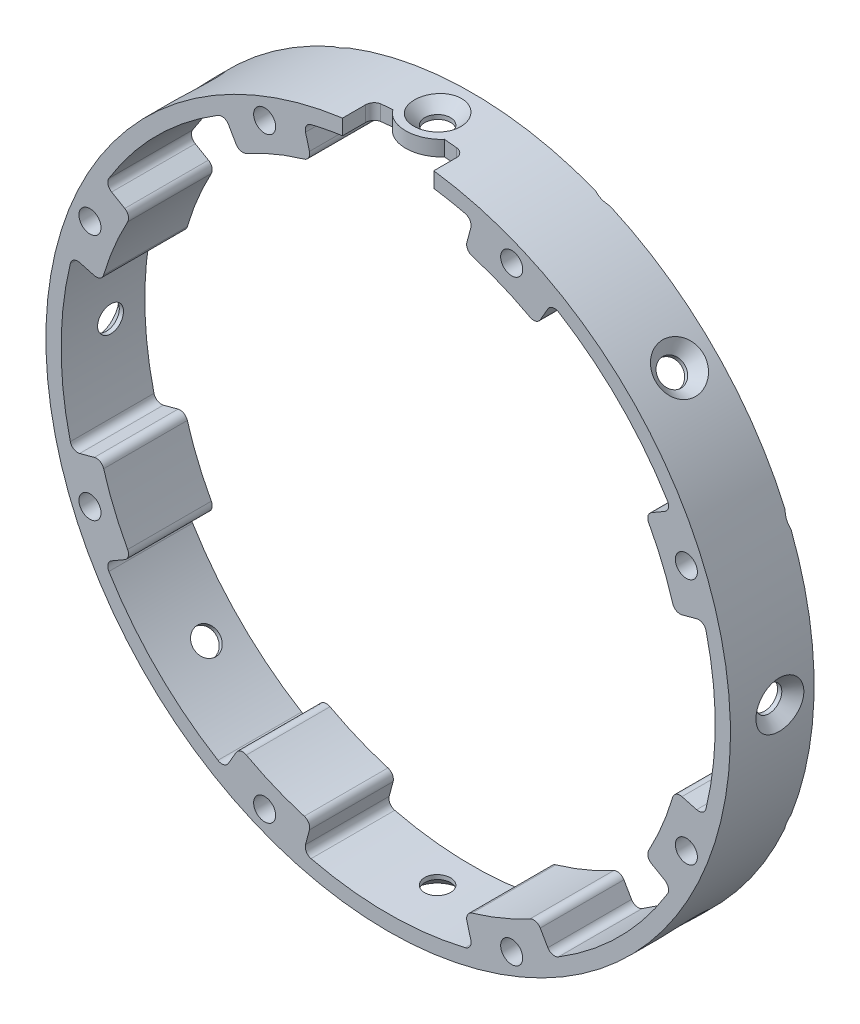
SolidWorks part; units mm, degrees
ref_plane "前视基准面" through (0, 0, 0) normal (0, 0, 1) x (1, 0, 0)
ref_plane "上视基准面" through (0, 0, 0) normal (0, 1, 0) x (1, 0, 0)
ref_plane "右视基准面" through (0, 0, 0) normal (1, 0, 0) x (0, 0, -1)
sketch "草图1" plane through (0, 0, 0) normal (0, 0, 1) x (1, 0, 0)
  line L0 (11.1292, 41.5348) -> (10.0939, 37.6711)
  line L17 (21.5, 37.2391) -> (19.5, 33.775)
  line L18 (-11.1292, 41.5348) -> (-10.0939, 37.6711)
  line L19 (37.2391, 21.5) -> (33.775, 19.5)
  line L20 (41.5348, 11.1292) -> (37.6711, 10.0939)
  line L21 (41.5348, -11.1292) -> (37.6711, -10.0939)
  line L22 (37.2391, -21.5) -> (33.775, -19.5)
  line L23 (21.5, -37.2391) -> (19.5, -33.775)
  line L24 (11.1292, -41.5348) -> (10.0939, -37.6711)
  line L25 (-11.1292, -41.5348) -> (-10.0939, -37.6711)
  line L26 (-21.5, -37.2391) -> (-19.5, -33.775)
  line L27 (-37.2391, -21.5) -> (-33.775, -19.5)
  line L28 (-41.5348, -11.1292) -> (-37.6711, -10.0939)
  line L29 (-41.5348, 11.1292) -> (-37.6711, 10.0939)
  line L30 (-37.2391, 21.5) -> (-33.775, 19.5)
  line L31 (-21.5, 37.2391) -> (-19.5, 33.775)
  circle A1 centre (0, 0) radius 45
  arc A3 (10.0939, 37.6711) -> (19.5, 33.775) centre (0, 0) cw
  arc A4 (11.1292, 41.5348) -> (-11.1292, 41.5348) centre (0, 0) ccw
  arc A21 (37.2391, 21.5) -> (21.5, 37.2391) centre (0, 0) ccw
  arc A22 (33.775, 19.5) -> (37.6711, 10.0939) centre (0, 0) cw
  arc A23 (41.5348, -11.1292) -> (41.5348, 11.1292) centre (0, 0) ccw
  arc A24 (37.6711, -10.0939) -> (33.775, -19.5) centre (0, 0) cw
  arc A25 (21.5, -37.2391) -> (37.2391, -21.5) centre (0, 0) ccw
  arc A26 (19.5, -33.775) -> (10.0939, -37.6711) centre (0, 0) cw
  arc A27 (-11.1292, -41.5348) -> (11.1292, -41.5348) centre (0, 0) ccw
  arc A28 (-10.0939, -37.6711) -> (-19.5, -33.775) centre (0, 0) cw
  arc A29 (-37.2391, -21.5) -> (-21.5, -37.2391) centre (0, 0) ccw
  arc A30 (-33.775, -19.5) -> (-37.6711, -10.0939) centre (0, 0) cw
  arc A31 (-41.5348, 11.1292) -> (-41.5348, -11.1292) centre (0, 0) ccw
  arc A32 (-37.6711, 10.0939) -> (-33.775, 19.5) centre (0, 0) cw
  arc A33 (-21.5, 37.2391) -> (-37.2391, 21.5) centre (0, 0) ccw
  arc A34 (-19.5, 33.775) -> (-10.0939, 37.6711) centre (0, 0) cw
  point P51 (0, 0)
  point P56 (0, 0)
  dimension "D1" = 8
extrude "凸台-拉伸1" add sketch "草图1" against normal blind 11
hole_wizard "M3 锥坑平头的锥孔2" positions "3D草图3" profile "草图4" countersink size "M3" standard "BSI" end condition through all
sketch3d "3D草图3"
  point P67 (31.8198, 31.8198, -6.5)
  point P76 (45, 0, -6.5)
  point P83 (31.8198, -31.8198, -6.5)
  point P85 (-31.8198, 31.8198, -6.5)
  point P87 (-31.8198, -31.8198, -6.5)
  point P96 (0, -45, -6.5)
  point P98 (0, 45, -6.5)
  point P105 (-45, 0, -6.5)
sketch "草图4" plane through (31.8198, 31.8198, -6.5) normal (0, 0, 1) x (-0.7071, 0.7071, 0)
  line L0 (0, 0) -> (0, 108.6396)
  line L1 (0, 108.6396) -> (1.7, 108.6396)
  line L2 (1.7, 108.6396) -> (1.7, 1.45)
  line L3 (1.7, 1.45) -> (3.15, 0)
  line L5 (3.15, 0) -> (0, 0)
  line L6 (-1.7, 1.45) -> (-3.15, 0) construction
  line L11 (0, -6.35) -> (0, 107.95) construction
  dimension "通孔孔直径" = 3.4
  dimension "通孔孔深度" = 108.6396
  dimension "近端锥形沉头孔直径" = 6.3
  dimension "近端锥形沉头孔角度" = 90
ref_plane "基准面1" through (0, 45, 0) normal (0, 1, 0) x (1, 0, 0)
sketch "草图7" plane through (0, 45, 0) normal (0, 1, 0) x (1, 0, 0)
  line L0 (-6, 0) -> (6, 0)
  line L1 (-45, 0) -> (45, 0) construction
  line L2 (6, 0) -> (6, 4)
  line L3 (6, 4) -> (3.3749, 4)
  line L5 (-6, 0) -> (-6, 4)
  line L6 (-6, 4) -> (-3.3749, 4)
  arc A1 (3.3749, 4) -> (-3.3749, 4) centre (0, 6.5) cw
extrude "切除-拉伸1" cut sketch "草图7" against normal up to next
hole_wizard "M2.5 锥坑平头的锥孔2" positions "3D草图4" profile "草图8" countersink size "M2.5" standard "BSI" end condition up to next
sketch3d "3D草图4"
  point P13 (39.2044, 16.239, -11)
  point P19 (16.239, 39.2044, -11)
  point P21 (-16.239, 39.2044, -11)
  point P23 (39.2044, -16.239, -11)
  point P26 (-39.2044, 16.239, -11)
  point P28 (-39.2044, -16.239, -11)
  point P30 (-16.239, -39.2044, -11)
  point P32 (16.239, -39.2044, -11)
sketch "草图8" plane through (39.2044, 16.239, -11) normal (1, 0, 0) x (0, 1, 0)
  line L0 (0, 0) -> (0, 11)
  line L1 (0, 11) -> (1.45, 11)
  line L2 (1.45, 11) -> (1.45, 1.3)
  line L3 (1.45, 1.3) -> (2.75, 0)
  line L5 (2.75, 0) -> (0, 0)
  line L6 (-1.45, 1.3) -> (-2.75, 0) construction
  line L11 (0, -6.35) -> (0, 107.95) construction
  dimension "通孔孔直径" = 2.9
  dimension "通孔孔深度" = 11
  dimension "近端锥形沉头孔直径" = 5.5
  dimension "近端锥形沉头孔角度" = 90
fillet "圆角1" radius 1 32 edges at (-41.5348, -11.1292, -5.5) (-37.6711, -10.0939, -5.5) (-33.775, -19.5, -5.5) (-37.2391, -21.5, -5.5) (-21.5, -37.2391, -5.5) (-10.0939, -37.6711, -5.5) (-19.5, -33.775, -5.5) (-11.1292, -41.5348, -5.5) (11.1292, -41.5348, -5.5) (10.0939, -37.6711, -5.5) (19.5, -33.775, -5.5) (21.5, -37.2391, -5.5) (37.2391, -21.5, -5.5) (33.775, -19.5, -5.5) (37.6711, -10.0939, -5.5) (41.5348, -11.1292, -5.5) (41.5348, 11.1292, -5.5) (37.6711, 10.0939, -5.5) (33.775, 19.5, -5.5) (37.2391, 21.5, -5.5) (21.5, 37.2391, -5.5) (11.1292, 41.5348, -5.5) (10.0939, 37.6711, -5.5) (19.5, 33.775, -5.5) (-11.1292, 41.5348, -5.5) (-10.0939, 37.6711, -5.5) (-21.5, 37.2391, -5.5) (-19.5, 33.775, -5.5) (-37.2391, 21.5, -5.5) (-33.775, 19.5, -5.5) (-37.6711, 10.0939, -5.5) (-41.5348, 11.1292, -5.5)
fillet "圆角2" radius 1 2 edges at (-6, 43.5888, -4) (6, 43.5888, -4)
